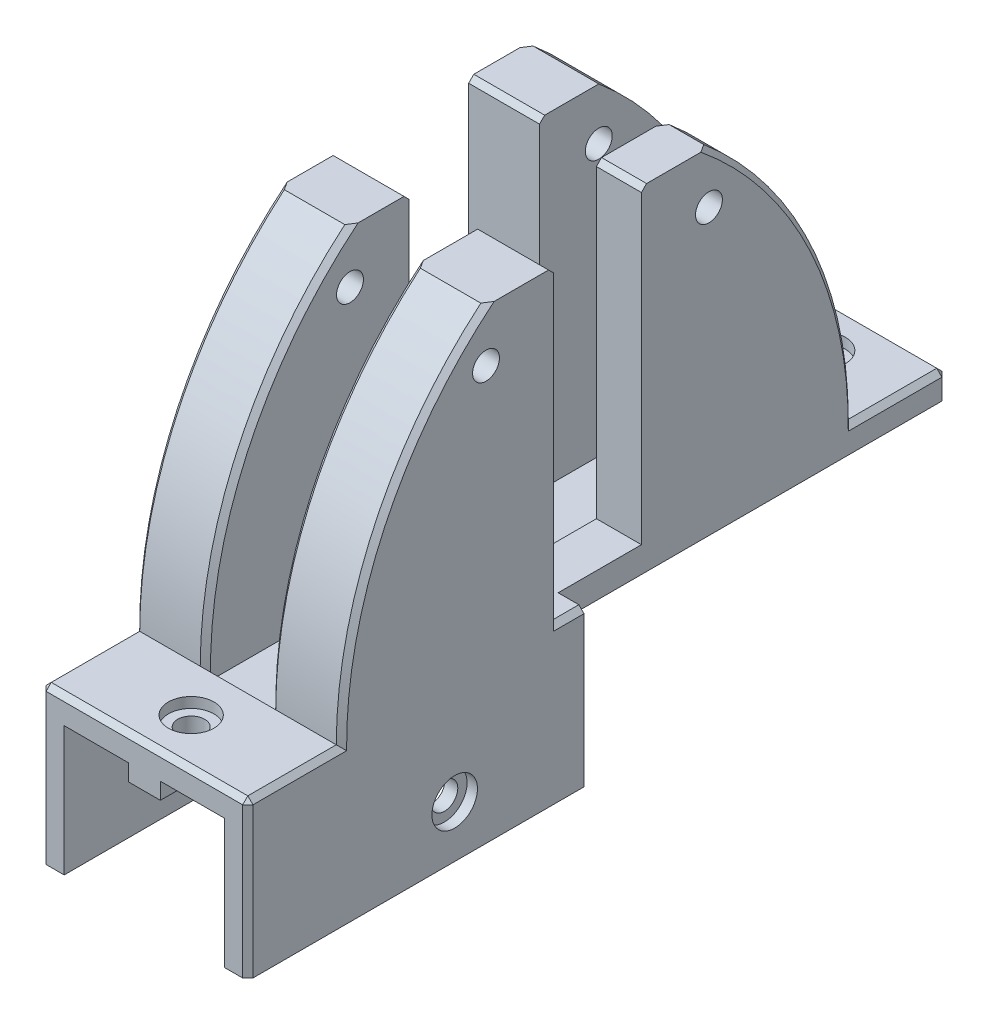
SolidWorks part; units mm, degrees
ref_plane "Front Plane" through (0, 0, 0) normal (0, 0, 1) x (1, 0, 0)
ref_plane "Top Plane" through (0, 0, 0) normal (0, 1, 0) x (1, 0, 0)
ref_plane "Right Plane" through (0, 0, 0) normal (1, 0, 0) x (0, 0, -1)
sketch "Sketch1" plane through (0, 0, 0) normal (0, 1, 0) x (1, 0, 0)
  line L0 (-68.9593, -88.8705) -> (-107.0593, -88.8705) construction
  line L1 (-71.3088, -191.8675) -> (-71.3088, -217.2675) construction
  line L2 (-96.0103, -136.4955) -> (-113.4093, -136.4955) construction
  line L3 (-107.0593, -266.9245) -> (-68.9593, -266.9245) construction
  line L4 (-80.0083, -138.5275) -> (-62.6093, -138.5275) construction
  line L5 (-88.0093, -88.8705) -> (-88.0093, -111.8575) construction
  line L6 (-107.0593, -266.9245) -> (-96.0103, -266.9245) construction
  line L7 (-96.0103, -111.8575) -> (-80.0083, -111.8575) construction
  line L8 (-96.0103, -243.9375) -> (-80.0083, -243.9375) construction
  line L9 (-80.0083, -243.9375) -> (-80.0083, -111.8575) construction
  line L10 (-96.0103, -111.8575) -> (-96.0103, -243.9375) construction
  line L11 (-88.0093, -243.9375) -> (-88.0093, -266.9245) construction
  line L12 (-71.3088, -138.5275) -> (-71.3088, -163.9275) construction
  line L13 (-68.9593, -266.9245) -> (-80.0083, -266.9245) construction
  line L14 (-104.7098, -136.4955) -> (-104.7098, -161.8955) construction
  line L15 (-80.0083, -163.9275) -> (-62.6093, -163.9275)
  line L16 (-104.7098, -193.8995) -> (-104.7098, -219.2995) construction
  line L17 (-68.9593, -88.8705) -> (-62.6093, -88.8705) construction
  line L18 (-107.0593, -88.8705) -> (-113.4093, -88.8705) construction
  line L19 (-113.4093, -88.8705) -> (-113.4093, -266.9245) construction
  line L20 (-113.4093, -266.9245) -> (-107.0593, -266.9245) construction
  line L21 (-62.6093, -88.8705) -> (-62.6093, -266.9245) construction
  line L22 (-62.6093, -266.9245) -> (-68.9593, -266.9245) construction
  line L23 (-96.0103, -219.2995) -> (-113.4093, -219.2995) construction
  line L24 (-80.0083, -217.2675) -> (-62.6093, -217.2675) construction
  line L25 (-62.6093, -163.9275) -> (-62.6093, -88.8705)
  line L26 (-62.6093, -88.8705) -> (-113.4093, -88.8705)
  line L27 (-113.4093, -88.8705) -> (-113.4093, -161.8955)
  line L28 (-113.4093, -161.8955) -> (-96.0103, -161.8955)
  line L29 (-96.0103, -161.8955) -> (-96.0103, -111.8575)
  line L30 (-96.0103, -111.8575) -> (-80.0083, -111.8575)
  line L31 (-80.0083, -111.8575) -> (-80.0083, -163.9275)
  line L32 (-113.4093, -193.8995) -> (-96.0103, -193.8995)
  line L33 (-96.0103, -193.8995) -> (-96.0103, -243.9375)
  line L34 (-96.0103, -243.9375) -> (-80.0083, -243.9375)
  line L35 (-80.0083, -243.9375) -> (-80.0083, -191.8675)
  line L36 (-80.0083, -191.8675) -> (-62.6093, -191.8675)
  line L37 (-62.6093, -191.8675) -> (-62.6093, -266.9245)
  line L38 (-62.6093, -266.9245) -> (-113.4093, -266.9245)
  line L39 (-113.4093, -266.9245) -> (-113.4093, -193.8995)
  circle A1 centre (-88.0093, -100.364) radius 3.302 construction
  circle A2 centre (-88.0093, -255.431) radius 3.302 construction
  circle A3 centre (-71.3088, -138.5275) radius 3.302 construction
  circle A4 centre (-104.7098, -136.4955) radius 3.302 construction
  circle A5 centre (-104.7098, -219.2995) radius 3.302 construction
  circle A6 centre (-71.3088, -217.2675) radius 3.302 construction
  point P10 (-104.7098, -177.8975)
  point P14 (-88.0093, -177.8975)
  point P17 (-88.0093, -111.8575)
  point P18 (-88.0093, -111.8575)
  point P21 (-88.0093, -243.9375)
  point P30 (-71.3088, -177.8975)
  point P55 (-113.4093, -125.383)
  dimension "D1" = 178.054
  dimension "D3" = 50.8
  dimension "D4" = 17.399
  dimension "D2" = 38.1
  dimension "D5" = 25.4
  dimension "D6" = 25.4
  dimension "D7" = 25.4
sketch "Sketch6" plane through (0, 0, 0) normal (0, 1, 0) x (1, 0, 0)
  line L0 (-113.4093, -88.8705) -> (-62.6093, -88.8705)
  line L1 (-62.6093, -88.8705) -> (-62.6093, -266.9245)
  line L2 (-62.6093, -266.9245) -> (-113.4093, -266.9245)
  line L3 (-113.4093, -266.9245) -> (-113.4093, -88.8705)
extrude "Boss-Extrude4" add sketch "Sketch6" against normal blind 6.35
sketch "Sketch7" plane through (-113.4093, 0, 0) normal (-1, 0, 0) x (0, 0, 1)
  line L0 (161.8999, 0) -> (161.8999, 48.26)
  line L1 (163.9275, 0) -> (88.8705, 0) construction
  line L2 (193.9023, 0) -> (193.9023, 48.26)
  line L3 (191.8675, 0) -> (266.9245, 0) construction
  line L4 (193.9023, 48.26) -> (193.9023, 55.118) construction
  line L5 (193.9023, 55.118) -> (193.9023, 69.5968) construction
  line L6 (161.8999, 48.26) -> (161.8999, 69.5968) construction
  line L8 (147.3447, 63.4629) -> (147.3447, 76.1629) construction
  line L9 (161.8999, 69.5968) -> (193.9023, 69.5968) construction
  line L10 (161.8999, 48.26) -> (161.8999, 76.1629)
  line L11 (88.8705, 0) -> (266.9245, 0) construction
  line L12 (177.8975, 0) -> (177.8975, 63.5) construction
  line L13 (111.8575, 0) -> (161.8999, 0)
  line L14 (193.9023, 0) -> (243.9375, 0)
  line L17 (147.3447, 0) -> (147.3447, 63.4629) construction
  line L18 (208.433, 0) -> (208.433, 63.5) construction
  line L19 (161.8999, 76.1629) -> (147.3447, 76.1629)
  line L20 (193.9023, 48.26) -> (193.9023, 76.1629)
  line L21 (193.9023, 76.1629) -> (208.433, 76.1629)
  line L22 (208.433, 63.5) -> (208.433, 76.1629) construction
  circle A5 centre (147.3447, 63.4629) radius 3.302 construction
  circle A6 centre (208.433, 63.5) radius 3.302 construction
  arc A7 (147.3447, 76.1629) -> (111.8575, 0) centre (211.9331, -0.2802) ccw
  arc A8 (208.433, 76.1629) -> (243.9375, 0) centre (143.862, -0.2948) cw
  dimension "D2" = 63.4629
  dimension "D3" = 100.076
  dimension "D1" = 100.076
  dimension "D4" = 76.1629
  dimension "D5" = 76.1629
  dimension "D6" = 63.5
extrude "Boss-Extrude5" add sketch "Sketch7" against normal blind 17.399
sketch "Sketch11" plane through (-62.6093, 0, 0) normal (1, 0, 0) x (0, 0, -1)
  line L0 (-193.9023, 76.1629) -> (-161.8999, 76.1629) construction
  line L1 (-161.8999, 76.1629) -> (-147.3447, 76.1629) construction
  line L2 (-193.9023, 76.1629) -> (-208.433, 76.1629) construction
  line L3 (-191.8126, 0) -> (-191.8126, 76.1629)
  line L4 (-88.8705, 0) -> (-266.9245, 0) construction
  line L5 (-191.8126, 76.1629) -> (-208.433, 76.1629)
  line L6 (-163.9273, 0) -> (-163.9273, 76.1629)
  line L7 (-163.9273, 76.1629) -> (-147.3447, 76.1629)
  line L8 (-243.9375, 0) -> (-191.8126, 0)
  line L9 (-163.9273, 0) -> (-111.8575, 0)
  arc A0 (-208.433, 76.1629) -> (-243.9375, 0) centre (-143.862, -0.2948) ccw
  arc A1 (-147.3447, 76.1629) -> (-111.8575, 0) centre (-211.9331, -0.2802) cw
extrude "Boss-Extrude7" add sketch "Sketch11" against normal blind 17.399
sketch "Sketch12" plane through (-113.4093, 0, 0) normal (-1, 0, 0) x (0, 0, 1)
  circle A0 centre (147.3447, 63.4629) radius 3.302
  circle A1 centre (208.433, 63.5) radius 3.302
extrude "Cut-Extrude4" cut sketch "Sketch12" against normal up to surface (50.8 mm away) up to face at (-62.6093, 24.9803, 177.887)
sketch "Sketch13" plane through (0, 0, 0) normal (0, 1, 0) x (1, 0, 0)
  circle A0 centre (-88.0093, -100.364) radius 3.302
  circle A1 centre (-88.0093, -255.431) radius 3.302
extrude "Cut-Extrude5" cut sketch "Sketch13" against normal up to surface (6.35 mm away) up to face at (-88.0093, -6.35, 177.8975)
sketch "Sketch16" plane through (0, 0, 0) normal (0, 1, 0) x (1, 0, 0)
  line L0 (-96.0103, -111.8575) -> (-80.0083, -111.8575)
  line L1 (-80.0083, -111.8575) -> (-80.0083, -243.9375)
  line L2 (-80.0083, -243.9375) -> (-96.0103, -243.9375)
  line L3 (-96.0103, -243.9375) -> (-96.0103, -111.8575)
extrude "Cut-Extrude7" cut sketch "Sketch16" against normal blind 3
sketch "Sketch17" plane through (0, -6.35, 0) normal (0, -1, 0) x (1, 0, 0)
  line L0 (-91.9463, 266.9245) -> (-84.0723, 266.9245)
  line L1 (-62.6093, 266.9245) -> (-113.4093, 266.9245) construction
  line L2 (-84.0723, 266.9245) -> (-84.0723, 261.8372)
  line L3 (-84.0723, 261.8372) -> (-91.9463, 261.8372)
  line L4 (-91.9463, 261.8372) -> (-91.9463, 266.9245)
  line L5 (-91.9463, 177.8975) -> (-84.0723, 177.8975) construction
  line L6 (-84.0723, 177.8975) -> (-84.0723, 228.6975)
  line L7 (-84.0723, 228.6975) -> (-91.9463, 228.6975)
  line L8 (-91.9463, 228.6975) -> (-91.9463, 177.8975)
  line L9 (-91.9463, 177.8975) -> (-91.9463, 127.0975)
  line L10 (-91.9463, 127.0975) -> (-84.0723, 127.0975)
  line L11 (-84.0723, 127.0975) -> (-84.0723, 177.8975)
  line L17 (-88.0093, 261.8372) -> (-88.0093, 87.0901) construction
  line L18 (-88.0093, 88.8705) -> (-88.0093, 93.9505) construction
  line L19 (-62.6093, 88.8705) -> (-113.4093, 88.8705) construction
  line L20 (-91.8193, 93.9505) -> (-84.1993, 93.9505)
  line L21 (-91.8193, 93.9505) -> (-91.8193, 88.8705)
  line L22 (-91.8193, 88.8705) -> (-84.1993, 88.8705)
  line L23 (-84.1993, 88.8705) -> (-84.1993, 93.9505)
  point P5 (-88.0093, 266.9245)
  point P12 (-88.0093, 177.8975)
  point P25 (-88.0093, 93.9505)
  dimension "D1" = 7.874
extrude "Boss-Extrude8" add sketch "Sketch17" along normal blind 4.064
sketch "Sketch18" plane through (0, -6.35, 0) normal (0, -1, 0) x (1, 0, 0)
  line L0 (-113.4093, 266.9245) -> (-62.6093, 266.9245) construction
  line L1 (-113.4093, 266.9245) -> (-107.0593, 266.9245) construction
  line L2 (-62.6093, 266.9245) -> (-68.9593, 266.9245) construction
  line L3 (-107.0593, 266.9245) -> (-107.0593, 88.8705)
  line L4 (-91.8193, 88.8705) -> (-113.4093, 88.8705) construction
  line L5 (-107.0593, 88.8705) -> (-113.4093, 88.8705)
  line L6 (-113.4093, 88.8705) -> (-113.4093, 266.9245)
  line L7 (-113.4093, 266.9245) -> (-107.0593, 266.9245)
  line L12 (-62.6093, 266.9245) -> (-68.9593, 266.9245)
  line L13 (-68.9593, 266.9245) -> (-68.9593, 133.5745)
  line L14 (-68.9593, 133.5745) -> (-62.6093, 133.5745)
  line L15 (-62.6093, 266.9245) -> (-62.6093, 88.8705) construction
  line L16 (-62.6093, 133.5745) -> (-62.6093, 266.9245)
  dimension "D1" = 50.8
extrude "Boss-Extrude9" add sketch "Sketch18" along normal blind 31.75
sketch "Sketch22" plane through (-113.4093, 0, 0) normal (-1, 0, 0) x (0, 0, 1)
  line L0 (266.9245, 0) -> (266.9245, -6.35) construction
  line L1 (266.9245, -6.35) -> (266.9245, -44.45) construction
  line L2 (266.9245, -25.4) -> (88.8705, -25.4) construction
  line L3 (88.8705, -38.1) -> (88.8705, 0) construction
  line L4 (88.8705, -25.4) -> (139.6705, -25.4) construction
  line L5 (266.9245, -25.4) -> (216.1245, -25.4) construction
  circle A0 centre (139.6705, -25.4) radius 3.302
  circle A1 centre (216.1245, -25.4) radius 3.302
  dimension "D1" = 19.05
extrude "Cut-Extrude12" cut sketch "Sketch22" against normal up to surface (6.35 mm away) up to face at (-107.0593, -22.225, 177.8975)
sketch "Sketch23" plane through (-113.4093, 0, 0) normal (-1, 0, 0) x (0, 0, 1)
  circle A0 centre (139.6705, -25.4) radius 5.588
  circle A1 centre (216.1245, -25.4) radius 5.588
extrude "Cut-Extrude13" cut sketch "Sketch23" against normal blind 2.54
sketch "Sketch19" plane through (-62.6093, 0, 0) normal (1, 0, 0) x (0, 0, -1)
  line L0 (-266.9245, -6.35) -> (-133.5745, -6.35) construction
  line L2 (-216.1245, -25.4) -> (-216.1245, -6.35) construction
  circle A3 centre (-216.1245, -25.4) radius 3.302
extrude "Cut-Extrude8" cut sketch "Sketch19" against normal up to surface (6.35 mm away) up to face at (-68.9593, -22.225, 200.2495)
sketch "Sketch20" plane through (0, 0, 0) normal (0, 1, 0) x (1, 0, 0)
  circle A0 centre (-88.0093, -100.364) radius 5.588
  circle A1 centre (-88.0093, -255.431) radius 5.588
extrude "Cut-Extrude9" cut sketch "Sketch20" against normal blind 2.54
sketch "Sketch21" plane through (-62.6093, 0, 0) normal (1, 0, 0) x (0, 0, -1)
  circle A3 centre (-216.1245, -25.4) radius 5.588
extrude "Cut-Extrude11" cut sketch "Sketch21" against normal blind 2.54
sketch "Sketch24" plane through (-62.6093, 0, 0) normal (1, 0, 0) x (0, 0, -1)
  line L7 (-184.3745, 32.9829) -> (-184.3745, -38.1)
  line L8 (-133.5745, -38.1) -> (-266.9245, -38.1) construction
  line L9 (-184.3745, -38.1) -> (-88.8705, -38.1)
  line L10 (-88.8705, -38.1) -> (-88.8705, 32.9829)
  line L12 (-184.3745, 32.9829) -> (-184.3745, 76.1629)
  line L13 (-184.3745, 76.1629) -> (-88.8705, 76.1629)
  line L14 (-88.8705, 76.1629) -> (-88.8705, 32.9829)
extrude "Fit Cut" cut sketch "Sketch24" against normal blind 6.35
chamfer "Chamfer3" distance 1.27 7 edges at (-68.9593, 41.9862, 121.2206) (-80.0083, 41.9862, 121.2206) (-62.6093, 41.9885, 234.5666) (-96.0103, 41.9885, 234.5666) (-80.0083, 41.9885, 234.5666) (-113.4093, 41.9885, 234.5666) (-113.4093, 41.9862, 121.2206)
chamfer "Chamfer4" distance 1.27 10 edges at (-68.9593, -3.175, 88.8705) (-113.4093, -19.05, 88.8705) (-68.9593, 0, 100.999) (-113.4093, 0, 100.999) (-91.1843, 0, 88.8705) (-62.6093, -19.05, 266.9245) (-113.4093, -19.05, 266.9245) (-62.6093, 0, 254.796) (-113.4093, 0, 254.796) (-88.0093, 0, 266.9245)
chamfer "Chamfer5" distance 1.27 6 edges at (-62.6093, 0, 188.0936) (-113.4093, 0, 177.9011) (-104.7098, 76.1629, 161.8999) (-74.4838, 76.1629, 163.9273) (-104.7098, 76.1629, 193.9023) (-71.3088, 76.1629, 191.8126)
sketch "Sketch25" plane through (0, 0, 266.9245) normal (0, 0, 1) x (1, 0, 0)
  line L0 (-107.0593, -6.35) -> (-107.6943, -6.35)
  line L1 (-107.6943, -6.35) -> (-107.6943, -38.1)
  line L2 (-107.0593, -38.1) -> (-112.1393, -38.1) construction
  line L3 (-107.6943, -38.1) -> (-107.0593, -38.1)
  line L4 (-107.0593, -38.1) -> (-107.0593, -6.35)
  line L5 (-68.9593, -6.35) -> (-68.3243, -6.35)
  line L6 (-68.3243, -6.35) -> (-68.3243, -38.1)
  line L7 (-63.8793, -38.1) -> (-68.9593, -38.1) construction
  line L8 (-68.3243, -38.1) -> (-68.9593, -38.1)
  line L9 (-68.9593, -38.1) -> (-68.9593, -6.35)
  dimension "D1" = 0.635
  dimension "D2" = 0.635
extrude "Cut-Extrude14" cut sketch "Sketch25" against normal up to surface (178.054 mm away) up to face at (-93.0893, -12.4968, 88.8705)
